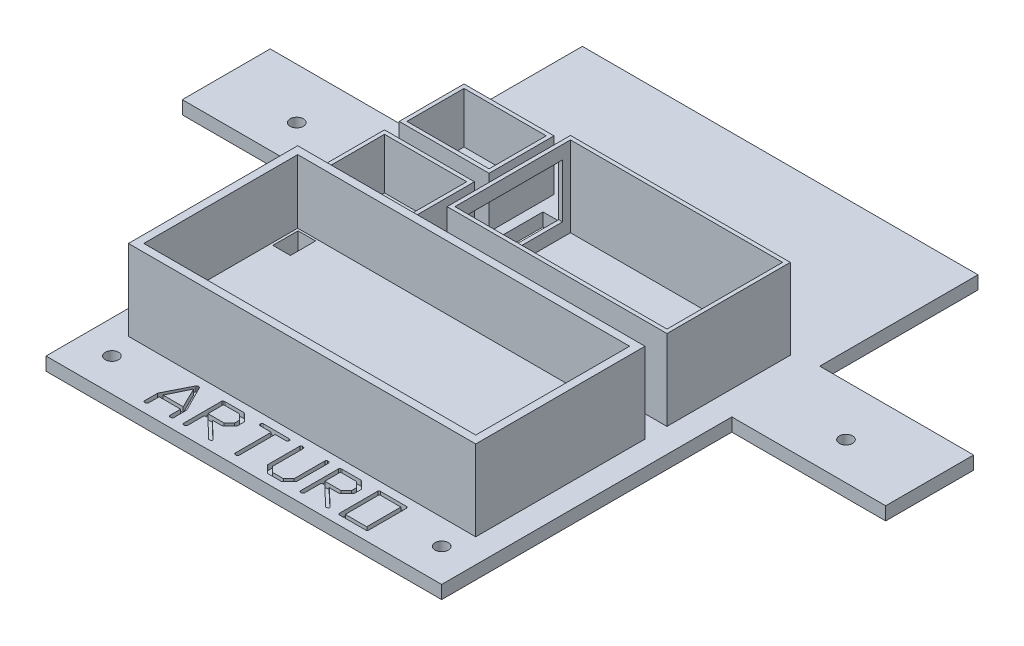
SolidWorks part; units mm, degrees
ref_plane "Front Plane" through (0, 0, 0) normal (0, 0, 1) x (1, 0, 0)
ref_plane "Top Plane" through (0, 0, 0) normal (0, 1, 0) x (1, 0, 0)
ref_plane "Right Plane" through (0, 0, 0) normal (1, 0, 0) x (0, 0, -1)
sketch "Sketch1" plane through (0, 0, 0) normal (0, 1, 0) x (1, 0, 0)
  line L1 (0, 0) -> (90, 0)
  line L2 (0, 0) -> (0, 145)
  line L3 (0, 145) -> (90, 145)
  line L4 (90, 0) -> (90, 145)
  dimension "D1" = 145
  dimension "D2" = 90
extrude "Boss-Extrude1" add sketch "Sketch1" along normal blind 3 contours L2 L3 L4 L1
sketch "Sketch3" plane through (0, 3, 0) normal (0, 1, 0) x (1, 0, 0)
  line L0 (90, 0) -> (90, 145) construction
  line L1 (90, 86) -> (125, 86)
  line L2 (90, 86) -> (90, 66)
  line L3 (90, 66) -> (125, 66)
  line L4 (125, 86) -> (125, 66)
  line L5 (0, 0) -> (90, 0) construction
  line L6 (0, 0) -> (0, 145) construction
  line L7 (0, 86) -> (-35, 86)
  line L8 (0, 86) -> (0, 66)
  line L9 (0, 66) -> (-35, 66)
  line L10 (-35, 86) -> (-35, 66)
  dimension "D1" = 66
extrude "Boss-Extrude2" add sketch "Sketch3" against normal blind 3
sketch "Sketch2" plane through (0, 3, 0) normal (0, 1, 0) x (1, 0, 0)
  circle A0 centre (7.5, 7.5) radius 1.5
  circle A1 centre (82.5, 7.5) radius 1.5
  point P10 (0, 0)
  dimension "D3" = 3
extrude "Cut-Extrude1" cut sketch "Sketch2" against normal blind 3
sketch "Sketch5" plane through (0, 3, 0) normal (0, 1, 0) x (1, 0, 0)
  line L0 (0, 0) -> (90, 0) construction
  line L1 (5.5, 51.75) -> (84.5, 51.75)
  line L2 (5.5, 51.75) -> (5.5, 13.25)
  line L3 (5.5, 13.25) -> (84.5, 13.25)
  line L4 (84.5, 51.75) -> (84.5, 13.25)
  line L5 (45, 145) -> (45, 77.1413) construction
  line L7 (0, 145) -> (90, 145) construction
  point P9 (5.5, 32.5)
  point P11 (45, 51.75)
  dimension "D1" = 13.25
  dimension "D2" = 0
  dimension "D3" = 38.5
  dimension "D4" = 79
extrude "Boss-Extrude3" add sketch "Sketch5" along normal blind 18.3
sketch "Sketch7" plane through (0, 21.3, 0) normal (0, 1, 0) x (1, 0, 0)
  line L0 (45, 13.25) -> (45, 51.75) construction
  line L5 (5.5, 13.25) -> (84.5, 13.25) construction
  line L6 (84.5, 51.75) -> (5.5, 51.75) construction
  line L8 (82.75, 15) -> (7.25, 15)
  line L9 (82.75, 15) -> (82.75, 50)
  line L10 (82.75, 50) -> (7.25, 50)
  line L11 (7.25, 15) -> (7.25, 50)
  line L12 (82.75, 15) -> (7.25, 50) construction
  line L13 (82.75, 50) -> (7.25, 15) construction
  point P6 (45, 32.5)
extrude "Cut-Extrude3" cut sketch "Sketch7" against normal blind 14.5
sketch "Sketch14" plane through (0, 6.8, 0) normal (0, 1, 0) x (1, 0, 0)
  line L1 (11.8026, 49.53) -> (7.8026, 49.53)
  line L2 (11.8026, 49.53) -> (11.8026, 43.798)
  line L3 (11.8026, 43.798) -> (7.8026, 43.798)
  line L4 (7.8026, 49.53) -> (7.8026, 43.798)
  line L5 (11.8026, 49.53) -> (7.8026, 43.798) construction
  line L6 (11.8026, 43.798) -> (7.8026, 49.53) construction
  point P0 (9.8026, 46.664)
  point P5 (9.537, 42.959)
extrude "Cut-Extrude6" cut sketch "Sketch14" against normal through all
sketch "Sketch8" plane through (0, 3, 0) normal (0, 1, 0) x (1, 0, 0)
  line L0 (5.5, 36.7092) -> (0, 36.7092) construction
  line L1 (5.5, 71.5) -> (25.95, 71.5)
  line L2 (5.5, 71.5) -> (5.5, 56.75)
  line L3 (5.5, 56.75) -> (25.95, 56.75)
  line L4 (25.95, 71.5) -> (25.95, 56.75)
  line L5 (5.5, 51.75) -> (5.5, 13.25) construction
  line L6 (84.5, 51.75) -> (5.5, 51.75) construction
  line L7 (5.5, 89.5891) -> (25.95, 89.5891)
  line L8 (5.5, 89.5891) -> (5.5, 74.8391)
  line L9 (5.5, 74.8391) -> (25.95, 74.8391)
  line L10 (25.95, 89.5891) -> (25.95, 74.8391)
  line L11 (0, 0) -> (0, 66) construction
  line L12 (0, 86) -> (0, 145) construction
  dimension "D1" = 20.45
  dimension "D2" = 5
  dimension "D3" = 14.75
  dimension "D4" = 5.5
  dimension "D5" = 5.5
extrude "Boss-Extrude4" add sketch "Sketch8" along normal blind 11.55
sketch "Sketch11" plane through (0, 14.55, 0) normal (0, 1, 0) x (1, 0, 0)
  line L1 (24.475, 68.375) -> (14.775, 68.375)
  line L2 (24.475, 68.375) -> (24.475, 59.875)
  line L3 (24.475, 59.875) -> (14.775, 59.875)
  line L4 (14.775, 68.375) -> (14.775, 59.875)
  line L5 (25.95, 56.75) -> (25.95, 71.5) construction
  line L6 (28.0802, 71.5) -> (28.0802, 56.75) construction
  line L7 (25.95, 71.5) -> (5.5, 71.5) construction
  line L8 (5.5, 56.75) -> (25.95, 56.75) construction
  line L10 (24.475, 77.9641) -> (14.775, 77.9641)
  line L11 (24.475, 77.9641) -> (24.475, 86.4641)
  line L12 (24.475, 86.4641) -> (14.775, 86.4641)
  line L13 (14.775, 77.9641) -> (14.775, 86.4641)
  line L14 (25.95, 89.5891) -> (5.5, 89.5891) construction
  line L15 (5.5, 74.8391) -> (25.95, 74.8391) construction
  line L16 (25.95, 74.8391) -> (25.95, 89.5891) construction
  point P12 (28.0802, 64.125)
  point P13 (24.475, 64.125)
  dimension "D1" = 9.7
  dimension "D2" = 1.475
  dimension "D3" = 0
  dimension "D4" = 8.5
  dimension "D5" = 1.475
  dimension "D6" = 3.125
  dimension "D7" = 3.125
  dimension "D8" = 3.125
  dimension "D9" = 3.125
  dimension "D10" = 1.475
  dimension "D11" = 9.7
extrude "Cut-Extrude4" cut sketch "Sketch11" against normal through all
sketch "Sketch12" plane through (0, 14.55, 0) normal (0, 1, 0) x (1, 0, 0)
  line L1 (24.475, 68.375) -> (14.775, 68.375)
  line L2 (24.475, 68.375) -> (24.475, 59.875)
  line L3 (24.475, 59.875) -> (14.775, 59.875)
  line L4 (14.775, 68.375) -> (14.775, 59.875)
extrude "Boss-Extrude5" add sketch "Sketch12" against normal blind 11.55
sketch "Sketch13" plane through (0, 14.55, 0) normal (0, 1, 0) x (1, 0, 0)
  line L0 (25.95, 64.125) -> (5.5, 64.125) construction
  line L1 (25.95, 56.75) -> (25.95, 71.5) construction
  line L2 (5.5, 71.5) -> (5.5, 56.75) construction
  line L4 (6.375, 70.625) -> (25.075, 70.625)
  line L5 (6.375, 70.625) -> (6.375, 57.625)
  line L6 (6.375, 57.625) -> (25.075, 57.625)
  line L7 (25.075, 70.625) -> (25.075, 57.625)
  line L8 (6.375, 70.625) -> (25.075, 57.625) construction
  line L9 (6.375, 57.625) -> (25.075, 70.625) construction
  line L13 (6.375, 88.7141) -> (25.075, 88.7141)
  line L14 (6.375, 88.7141) -> (6.375, 75.7141)
  line L15 (6.375, 75.7141) -> (25.075, 75.7141)
  line L16 (25.075, 88.7141) -> (25.075, 75.7141)
  line L17 (25.95, 74.8391) -> (25.95, 89.5891) construction
  line L18 (25.95, 89.5891) -> (5.5, 89.5891) construction
  line L19 (5.5, 74.8391) -> (25.95, 74.8391) construction
  point P6 (15.725, 64.125)
  dimension "D1" = 0.875
  dimension "D2" = 0.875
  dimension "D3" = 0.875
extrude "Cut-Extrude5" cut sketch "Sketch13" against normal blind 11.55
sketch "Sketch19" plane through (0, 3, 0) normal (0, 1, 0) x (1, 0, 0)
  line L0 (84.5, 51.75) -> (5.5, 51.75) construction
  line L1 (84.5, 56.75) -> (34.5, 56.75)
  line L2 (84.5, 56.75) -> (84.5, 84.8)
  line L3 (84.5, 84.8) -> (34.5, 84.8)
  line L4 (34.5, 56.75) -> (34.5, 84.8)
  line L7 (90, 0) -> (90, 66) construction
  dimension "D1" = 28.05
  dimension "D2" = 50
  dimension "D3" = 5
  dimension "D4" = 5.5
extrude "Boss-Extrude6" add sketch "Sketch19" along normal blind 18.3
sketch "Sketch20" plane through (0, 21.3, 0) normal (0, 1, 0) x (1, 0, 0)
  line L0 (84.5, 70.775) -> (34.5, 70.775) construction
  line L1 (84.5, 56.75) -> (84.5, 84.8) construction
  line L2 (34.5, 84.8) -> (34.5, 56.75) construction
  line L4 (83.625, 83.925) -> (35.375, 83.925)
  line L5 (83.625, 83.925) -> (83.625, 57.625)
  line L6 (83.625, 57.625) -> (35.375, 57.625)
  line L7 (35.375, 83.925) -> (35.375, 57.625)
  line L8 (83.625, 83.925) -> (35.375, 57.625) construction
  line L9 (83.625, 57.625) -> (35.375, 83.925) construction
  point P6 (59.5, 70.775)
extrude "Cut-Extrude7" cut sketch "Sketch20" against normal blind 18.3
sketch "Sketch22" plane through (34.5, 0, 0) normal (-1, 0, 0) x (0, 0, 1)
  line L0 (-70.775, 21.3) -> (-70.775, 3) construction
  line L1 (-84.8, 21.3) -> (-56.75, 21.3) construction
  line L2 (-84.8, 3) -> (-56.75, 3) construction
  line L4 (-82.1319, 6.0463) -> (-59.4181, 6.0463)
  line L5 (-82.1319, 6.0463) -> (-82.1319, 18.2537)
  line L6 (-82.1319, 18.2537) -> (-59.4181, 18.2537)
  line L7 (-59.4181, 6.0463) -> (-59.4181, 18.2537)
  line L8 (-82.1319, 6.0463) -> (-59.4181, 18.2537) construction
  line L9 (-82.1319, 18.2537) -> (-59.4181, 6.0463) construction
  point P6 (-70.775, 12.15)
extrude "Cut-Extrude8" cut sketch "Sketch22" against normal blind 1.75
sketch "Sketch23" plane through (0, 3, 0) normal (0, 1, 0) x (1, 0, 0)
  line L1 (32.8406, 84.9149) -> (28.1238, 84.9149)
  line L2 (32.8406, 84.9149) -> (32.8406, 57.6824)
  line L3 (32.8406, 57.6824) -> (28.1238, 57.6824)
  line L4 (28.1238, 84.9149) -> (28.1238, 57.6824)
extrude "Cut-Extrude9" cut sketch "Sketch23" against normal through all
sketch "Sketch24" plane through (0, 3, 0) normal (0, 1, 0) x (1, 0, 0)
  text T0 "ARTURO" font "SWTxt" height in points 36
extrude "Cut-Extrude10" cut sketch "Sketch24" against normal blind 1.2
sketch "Sketch25" plane through (0, 3, 0) normal (0, 1, 0) x (1, 0, 0)
  circle A0 centre (-17.4688, 74.5) radius 1.5
  circle A1 centre (107.4688, 74.5) radius 1.5
extrude "Cut-Extrude11" cut sketch "Sketch25" against normal through all
sketch "Sketch26" plane through (0, 3, 0) normal (0, 1, 0) x (1, 0, 0)
  line L0 (90, 86) -> (90, 145) construction
  line L1 (0, 145) -> (90, 145)
  line L2 (0, 145) -> (0, 122)
  line L3 (0, 122) -> (90, 122)
  line L4 (90, 145) -> (90, 122)
extrude "Cut-Extrude12" cut sketch "Sketch26" against normal through all
